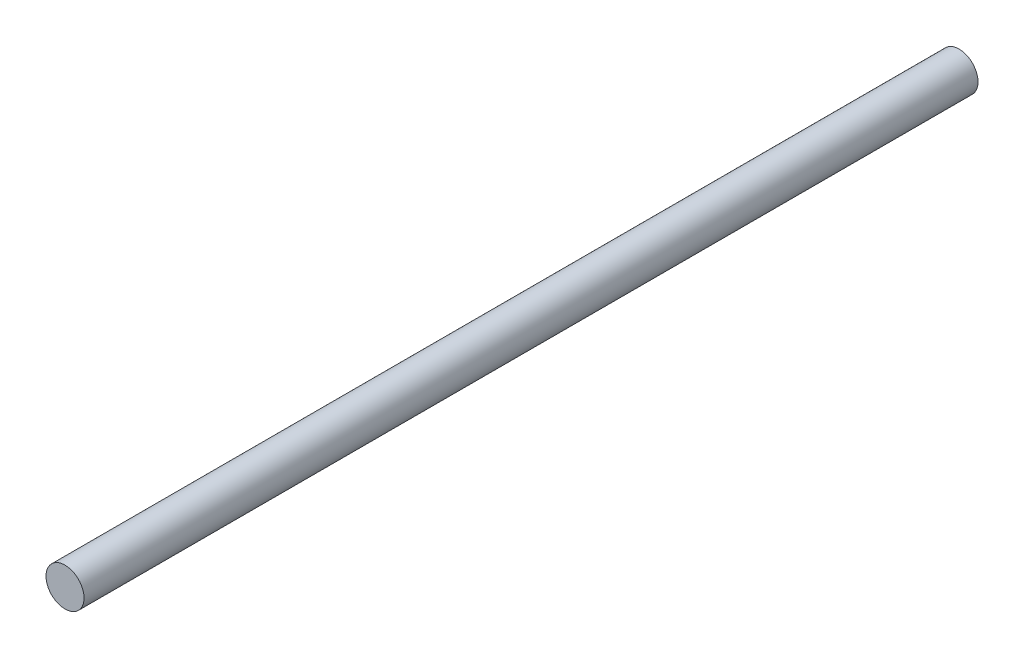
SolidWorks part; units mm, degrees
ref_plane "Front Plane" through (0, 0, 0) normal (0, 0, 1) x (1, 0, 0)
ref_plane "Top Plane" through (0, 0, 0) normal (0, 1, 0) x (1, 0, 0)
ref_plane "Right Plane" through (0, 0, 0) normal (1, 0, 0) x (0, 0, -1)
sketch "Sketch1" plane through (0, 0, 0) normal (0, 0, 1) x (1, 0, 0)
  circle A0 centre (0, 0) radius 5
  dimension "D1" = 10
extrude "Boss-Extrude1" add sketch "Sketch1" along normal blind 235
